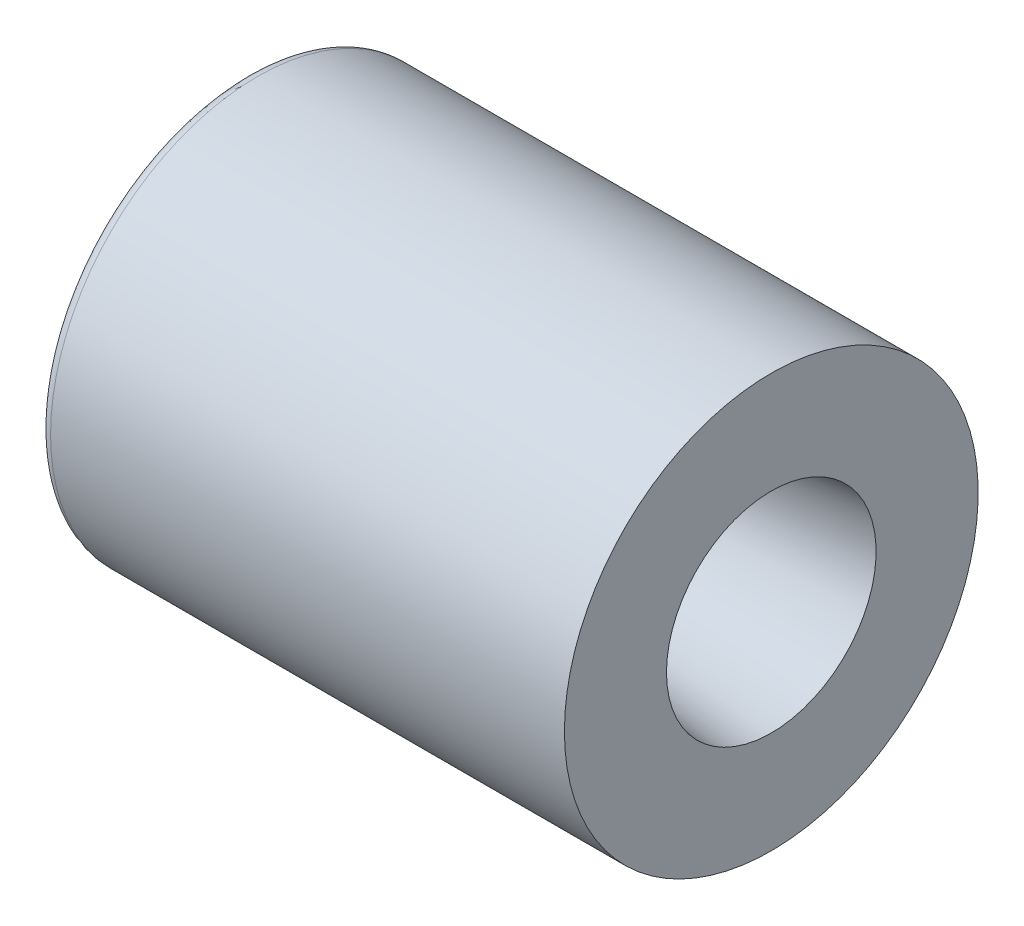
SolidWorks part; units mm, degrees
ref_plane "Front Plane" through (0, 0, 0) normal (0, 0, 1) x (1, 0, 0)
ref_plane "Top Plane" through (0, 0, 0) normal (0, 1, 0) x (1, 0, 0)
ref_plane "Right Plane" through (0, 0, 0) normal (1, 0, 0) x (0, 0, -1)
sketch "Sketch1" plane through (0, 0, 0) normal (0, 1, 0) x (1, 0, 0)
  line L0 (0, 0) -> (0, 2.286) construction
  line L1 (0, 2.286) -> (0, 5.3848)
  line L2 (0, 9.525) -> (24.1665, 9.525)
  line L3 (24.1665, 9.525) -> (24.1665, 4.826)
  line L4 (24.1665, 4.826) -> (0, 2.286)
  line L5 (0, 0) -> (24.1665, 0) construction
  line L6 (24.1665, 0) -> (24.1665, 4.826) construction
  line L7 (0, 5.3848) -> (1.905, 5.3848)
  line L8 (1.905, 5.3848) -> (1.905, 8.001)
  line L9 (1.905, 8.001) -> (0, 8.001)
  line L10 (0, 8.001) -> (0, 9.525)
  dimension "D1" = 2.286
  dimension "D2" = 4.826
  dimension "D3" = 6
  dimension "D4" = 9.525
  dimension "D5" = 5.3848
  dimension "D6" = 8.001
  dimension "D7" = 1.905
revolve "Revolve1" add sketch "Sketch1" angle 360 about L5
fillet "Fillet1" radius 0.508 1 edges at (0, 0, 9.525)
equation "\"z\" = 8\t\t\t\t'number of blades"
equation "\"de\" = 0.43in\t\t\t'entrance eye diameter"
equation "\"de_length\" = 10mm\t\t'entrance eye consistent length"
equation "\"d_exit\" = 0.18in \t\t'throat aka d1"
equation "\"d2\" = 2.1in \t\t\t'outer diameter of the impeller"
equation "\"b2\" = .2in\t\t\t'tip height from disc surface at d2; slightly higher than d_exit"
equation "\"b1\" = \"b2\" + (\"d2\"/2 - \"de\"/2)*tan(\"theta\") \t\t\t'tip height from disc surface at inlet eye"
equation "\"theta\" = 12\t\t\t'angle of blades from inner to outer "
equation "\"ae\" = 3.14*(\"de\"^2)/4\t\t'entrance eye area'"
equation "\"ce\" = 3.14*\"de\"\t\t'entrance eye circumference"
equation "\"av_ratio\" = .325\t\t'ratio of av/ae at N_s of 470, range is .275 to .375, .325 ideal. High ratio means bigger area means smaller blades"
equation "\"av\" = \"ae\"*\"av_ratio\"\t\t'area between just two blades"
equation "\"s_open\" = \"av\"/\"b1\"\t\t'width of open area"
equation "\"s\"=\"ce\" - \"z\"*\"s_open\""
equation "\"min blade thickness\" = .15in"
equation "\"bearing OD\" = 30mm"
equation "\"bearing ID\"= 10mm"
equation "\"bearing depth\"= 9mm"
equation "\"bearing outer race thickness\"= 1mm"
equation "\"bearing inner race thickness\"= 1mm"
equation "\"bearing bore\" = \"bearing depth\" + 1mm"
equation "\"lower seal OD\" = .917in\t\t'this is https://www.mcmaster.com/#9281k121/=174001b"
equation "\"lower seal ID\"= .375in"
equation "\"lower seal depth\" = .625in + .218in"
equation "\"lower seal bore\" = \"lower seal depth\" + 1mm"
equation "\"upper seal OD\" = 1.125in\t'this is https://www.mcmaster.com/#5154t33/=173zuau, needs to be visually inspected before machining!"
equation "\"upper seal ID\"= 0.625in"
equation "\"upper seal depth\"= .25in\t'aka height; these values need to be confirmed by inspection!! We may want to compress the height."
equation "\"upper seal bore\" = \"upper seal depth\" + 1mm"
equation "\"big o-ring thickness\" = .139in"
equation "\"big o-ring OD\" = 2.734in"
equation "\"big o-ring ID\" = 3.012in"
equation "\"big o-ring groove depth\" = \"big o-ring thickness\"*4/5"
equation "\"impeller center height\" = \"impeller base thickness\" + \"b1\"\t'impeller height at de"
equation "\"impeller outer height\" = \"impeller base thickness\" + \"b2\"\t'impeller height at de"
equation "\"impeller upper clearance\"= .5mm"
equation "\"impeller horizontal clearance\"= (\"d2\"*1.15 - \"d2\")/2 \t\t'clearance based on D2-D3 ratio for circular volute, ranges 1.15 to 1.2"
equation "\"impeller bottom clearance\"= .5mm"
equation "\"impeller base thickness\"= 2mm"
equation "\"impeller dowel diameter\" = 2mm"
equation "\"impeller bolt head diameter\" = \"m4 head bore diameter\""
equation "\"impeller bolt head depth\" = 4mm"
equation "\"impeller bolt stop depth\" = 3mm"
equation "\"impeller bolt bore\" = \"m4 clearance\""
equation "\"impeller shaft bore depth\" = 12mm"
equation "\"impeller shaft bore\" = 8mm"
equation "\"impeller boss depth\" = \"impeller shaft bore depth\"+\"impeller bolt stop depth\"+\"impeller bolt head depth\"-\"impeller base thickness\""
equation "\"impeller boss diameter\" = \"upper seal ID\""
equation "\"impeller dowel length\" = 2mm*2 + \"impeller shaft bore\""
equation "\"coupler motor shaft hole ID\"= 8mm"
equation "\"coupler OD\"= 17mm"
equation "\"coupler length\"= 25mm"
equation "\"motor OD\" = 64mm"
equation "\"motor shaft diameter\"= 8mm"
equation "\"motor shaft pride\"= 32mm"
equation "\"motor to bearing plate distance\" = \"motor shaft pride\" + 2mm +\"coupler length\"/2"
equation "\"square plate bolt bore\" = \"m8 clearance\""
equation "\"square plate bolt head diameter\" = 13.5mm"
equation "\"square plate bolt head depth\" = 8mm"
equation "\"square plate bolt pattern diameter\"= 3.5in"
equation "\"motor mount center bore\"= \"coupler OD\"+ 4mm"
equation "\"motor mount post radius\"= ( 3 * \"square plate bolt bore\" ) / 2"
equation "\"motor mount m4 screw hole diameter\"= 4mm"
equation "\"motor mount m4 head diameter\"= 7.25mm"
equation "\"motor mount m4 head depth\"= 4mm"
equation "\"motor mount m4 pattern diamater\" = 30mm"
equation "\"motor mount plate thickness\"= 8mm + \"motor mount m4 head depth\""
equation "\"bearing plate stop ID\" = \"bearing OD\" - 4mm"
equation "\"bearing plate stop depth\" = 3mm"
equation "\"bearing plate thickness\" = \"bearing bore\" + \"bearing plate stop depth\" + \"shaft bearing stop length\""
equation "\"lower seal plate lip depth\" = 2mm"
equation "\"lower seal plate lip ID\" = \"lower seal OD\" - 3mm"
equation "\"lower seal plate thickness\" = \"lower seal plate lip depth\" + \"lower seal bore\""
equation "\"shaft coupler section diameter\" = 8mm"
equation "\"shaft coupler section length\" = \"motor to bearing plate distance\" - \"motor shaft pride\" - 2mm"
equation "\"shaft bearing section diameter\" = \"bearing ID\""
equation "\"shaft bearing section length\" = \"bearing plate stop depth\" + \"bearing depth\""
equation "\"shaft bearing stop diameter\" = \"bearing ID\" + 4mm"
equation "\"shaft bearing stop length\" = 3mm"
equation "\"shaft lower seal section diameter\" = \"lower seal ID\""
equation "\"shaft lower seal section length\" = \"lower seal plate thickness\" + 1mm"
equation "\"shaft impeller section diameter\" = \"impeller shaft bore\""
equation "\"shaft impeller section length\" = \"upper seal plate thickness\" + \"upper seal plate riser\" + \"impeller bottom clearance\" + \"impeller base thickness\" - \"impeller bolt head depth\" - \"impeller bolt stop depth\""
equation "\"upper seal plate thickness\" = \"upper seal plate pressure hole diameter\"+10mm"
equation "\"upper seal plate lip ID\" = \"upper seal OD\" - 3mm"
equation "\"upper seal plate riser\" = 6.59mm \t\t'this number needs to be read from the housing file"
equation "\"upper seal plate pressure hole diameter\" = .125in\t'this is 1/8 drill "
equation "\"upper seal plate pressure tap diameter\" = .328125in \t'this is 21/64 drill for a 1/8 ANPT tap"
equation "\"upper seal plate pressure tap grip\" = 5mm\t\t'this is the area around the tap so it doesn't crack"
equation "\"upper seal plate pressure tap depth\" = 12"
equation "\"impeller cavity center height\"= \"impeller bottom clearance\" + \"impeller upper clearance\" + \"impeller center height\""
equation "\"impeller cavity diameter\"= 2 * \"impeller horizontal clearance\" + \"d2\" \t\t\t\t\t\t\t\t\t'called D3 analytically"
equation "\"impeller cavity outer height\"= \"impeller bottom clearance\" + \"impeller upper clearance\" + \"impeller base thickness\" + \"b2\" \t\t'this is height at impeller diameter d2, not at d3"
equation "\"impeller housing thickness\"= \"impeller housing exit threaded diameter\" + 2*\"impeller housing outlet grip\""
equation "\"impeller housing diameter\" = \"square plate bolt pattern diameter\" + 2*\"motor mount post radius\""
equation "\"impeller housing bolt count\" = 8"
equation "\"impeller housing bolt diameter\" = \"m6 clearance\""
equation "\"impeller housing bolt pattern diameter\" = 3.5in"
equation "\"impeller housing threaded inlet diameter\" = 0.515625in \t'this is the 33/64 drill size for 9/16-18 fitting, expecting swagelok SS-8FK0-1-6STH fitting"
equation "\"impeller housing threaded inlet depth\"= 10mm"
equation "\"impeller housing exit threaded diameter\"= 0.515625in \t\t'this is the 33/64 drill size for 9/16-18 fitting, expecting swagelok SS-8FK0-1-6STH fitting"
equation "\"impeller housing exit threaded depth\"= 10mm"
equation "\"impeller housing diffuser conical angle\"=10"
equation "\"impeller housing diffuser tangent angle\"=5"
equation "\"impeller housing diffuser final diameter\" = .38in\t\t'aka d2'"
equation "\"impeller housing outlet grip\" = 5mm"
equation "\"end mill size\" = 0.375in\t'for 3/8 endmill"
equation "\"m4 clearance\" = 0.171875in \t'this is 11/64 bit for 4.36mm"
equation "\"m4 tap\" = 0.125in\t\t'this is 1/8 bit for 3.17mm"
equation "\"m4 head bore diameter\" = 7.5mm"
equation "\"m4 head bore depth\" = 5mm\t'actual is ~4mm"
equation "\"m6 clearance\" = 0.234375in\t'this is 15/64 bit = 5.95mm, could use 6mm bit, B bit for 6.04mm or 1/4 bit for 6.35mm"
equation "\"m6 tap\" = 5mm\t\t\t'5mm is appropriate, could use 13/64 or #5,6,7"
equation "\"m6 head bore diameter\" = 11mm\t\t"
equation "\"m6 head bore depth\" = 7mm\t'actual is 6mm"
equation "\"m8 clearance\" = 0.3125in\t'this is 5/16in for 7.93mm, could use 8mm, O,P, or 21/64"
equation "\"m8 tap\" = 0.265625in\t\t'this is 17/64 for 6.746875mm"
equation "\"m8 head bore diameter\" = 14mm"
equation "\"m8 head bore depth\" = 9mm\t'actual is 8mm"
equation "\"D1@Sketch1\"=\"d_exit\"/2"
equation "\"D2@Sketch1\"=\"impeller housing diffuser final diameter\"/2"
equation "\"diffuser cartridge OD\" =.75in"
equation "\"D4@Sketch1\"=\"diffuser cartridge OD\"/2"
